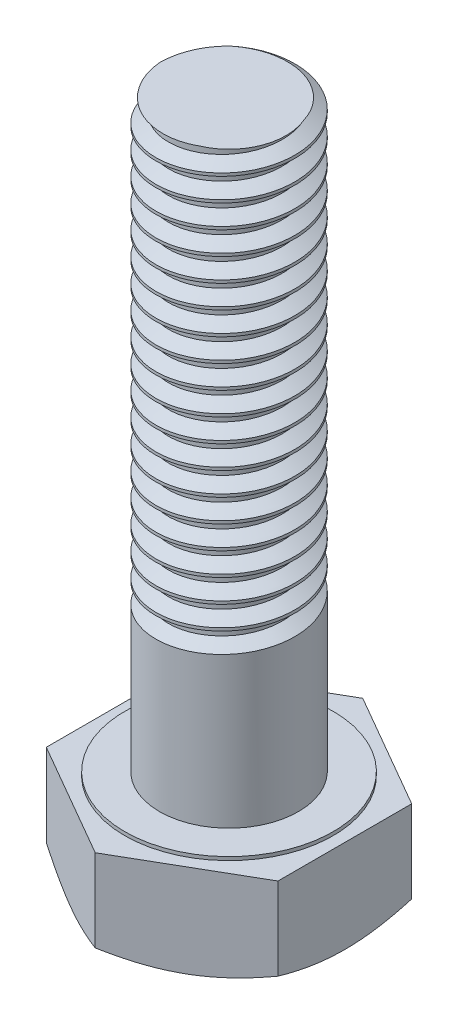
SolidWorks part; units mm, degrees
ref_plane "Front Plane" through (0, 0, 0) normal (0, 0, 1) x (1, 0, 0)
ref_plane "Top Plane" through (0, 0, 0) normal (0, 1, 0) x (1, 0, 0)
ref_plane "Right Plane" through (0, 0, 0) normal (1, 0, 0) x (0, 0, -1)
sketch "Sketch1" plane through (0, 0, 0) normal (0, 1, 0) x (1, 0, 0)
  line L0 (15.8992, 17.4162) -> (25.8992, 17.4162) construction
  line L1 (5, -2.8868) -> (5, 2.8868)
  line L2 (5, 2.8868) -> (0, 5.7735)
  line L3 (0, 5.7735) -> (-5, 2.8868)
  line L4 (-5, 2.8868) -> (-5, -2.8868)
  line L5 (-5, -2.8868) -> (0, -5.7735)
  line L6 (0, -5.7735) -> (5, -2.8868)
  line L7 (15.8992, 14.7438) -> (21.8992, 14.7438) construction
  line L8 (15.8992, 12.0228) -> (20.3992, 12.0228) construction
  line L10 (15.8992, 7.0188) -> (34.8992, 7.0188) construction
  line L11 (15.8992, 4.6566) -> (24.8992, 4.6566) construction
  line L12 (15.8992, 2.7865) -> (40.8992, 2.7865) construction
  line L13 (15.8992, 9.7748) -> (25.3992, 9.7748) construction
  circle A0 centre (0, 0) radius 5 construction
  dimension "bolt_diameter" = 6
  dimension "head_height" = 4.5
  dimension "thread_height" = 19
  dimension "extra_parts" = 9
  dimension "head_chamfer" = 9.5
  dimension "bolt_height" = 25
extrude "Boss-Extrude1" add sketch "Sketch1" along normal blind 4.15
sketch "Sketch2" plane through (0, 4.15, 0) normal (0, 1, 0) x (1, 0, 0)
  circle A0 centre (0, 0) radius 4.5
  dimension "extra_parts" = 9
extrude "Boss-Extrude2" add sketch "Sketch2" along normal blind 0.15
sketch "Sketch3" plane through (0, 4.3, 0) normal (0, 1, 0) x (1, 0, 0)
  circle A0 centre (0, 0) radius 3
  dimension "bolt_diameter" = 6
extrude "Boss-Extrude4" add sketch "Sketch3" along normal blind 25
sketch "Sketch7" plane through (0, 0, 0) normal (0, -1, 0) x (1, 0, 0)
  circle A0 centre (0, 0) radius 4.75
  dimension "head_chamfer" = 9.5
extrude "Cut-Extrude1" cut sketch "Sketch7" against normal blind 25 draft 60 flip side to cut
thread "Thread1" pitch 1 method cut profile "Thread Profile1" parameters start angle 0, offset 1, "thread_height"=19, pitch 1, diameter 6
ref_plane "Plane1" through (-3, 30.3, 0) normal (0, 0, 1) x (-1, 0, 0)
sketch "Thread Profile1" plane through (-3, 30.3, 0) normal (0, 0, 1) x (-1, 0, 0)
  line L0 (0, 0) -> (0, 1) construction
  line L11 (0, 0) -> (0, 0.875)
  line L12 (0, 0.875) -> (-0.5413, 0.5625)
  line L13 (-0.5413, 0.5625) -> (-0.5413, 0.3125)
  line L15 (-0.5413, 0.3125) -> (0, 0)
  line L17 (-0.5413, 0.4375) -> (0, 0.4375) construction
  point P2 (0, 0)
  dimension "Pitch" = 1
  dimension "Profile_Angle" = 60
  dimension "Profile_Land" = 0.25
  dimension "Profile_Height" = 0.5413
